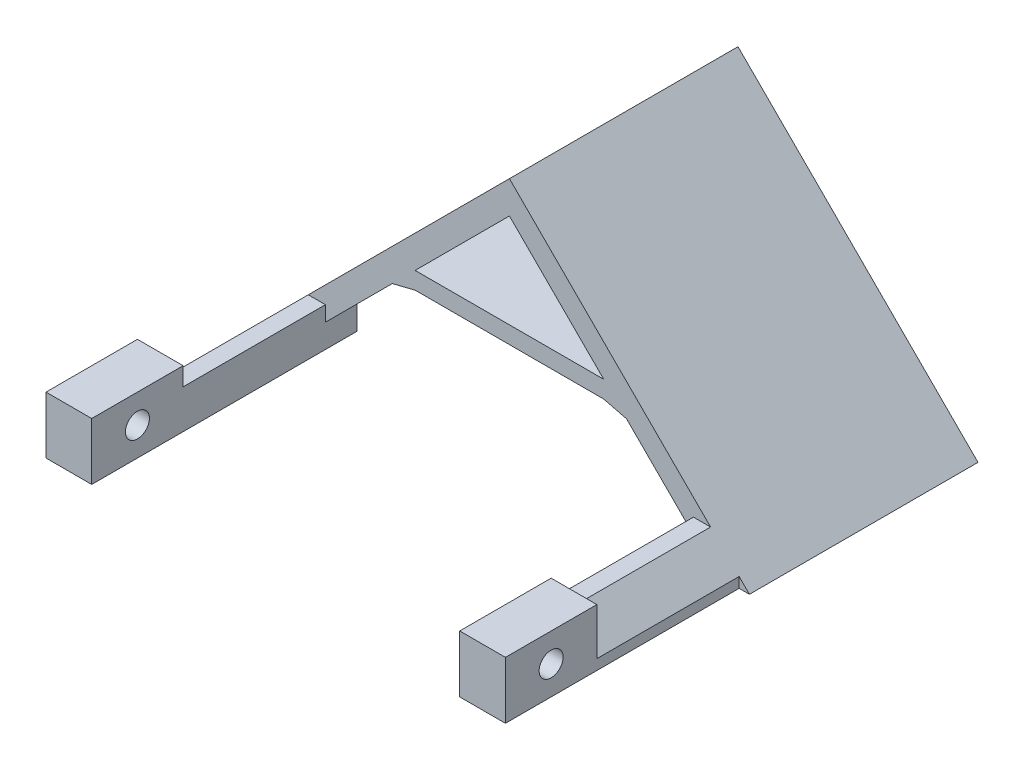
SolidWorks part; units mm, degrees
ref_plane "Front Plane" through (0, 0, 0) normal (0, 0, 1) x (1, 0, 0)
ref_plane "Top Plane" through (0, 0, 0) normal (0, 1, 0) x (1, 0, 0)
ref_plane "Right Plane" through (0, 0, 0) normal (1, 0, 0) x (0, 0, -1)
sketch "Sketch1" plane through (0, 0, 0) normal (0, 0, 1) x (1, 0, 0)
  line L1 (0, 0) -> (-42, -42)
  line L2 (0, -1000.3549) -> (0, 48999.6451) construction
  line L3 (-32.3431, -38) -> (-20.5, -26.1569)
  line L4 (32.3431, -38) -> (20.5, -26.1569)
  line L5 (0, 0) -> (42, -42)
  line L7 (-42, -42) -> (-16.5, -42) construction
  line L8 (-32.3431, -38) -> (-20.5, -38) construction
  line L9 (-34, -34) -> (34, -34) construction
  line L10 (-16.5, -42) -> (-16.5, -25.1569) construction
  line L11 (16.5, -42) -> (16.5, -25.1569) construction
  line L12 (16.5, -42) -> (42, -42) construction
  line L13 (20.5, -38) -> (32.3431, -38) construction
  line L14 (-20.5, -38) -> (-20.5, -26.1569) construction
  line L15 (20.5, -38) -> (20.5, -26.1569) construction
  line L16 (-16.5, -22.1569) -> (0, -5.6569)
  line L17 (16.5, -22.1569) -> (0, -5.6569)
  line L18 (16.5, -22.1569) -> (-16.5, -22.1569)
  line L19 (16.5, -25.1569) -> (-16.5, -25.1569)
  line L20 (-32.3431, -38) -> (-36.3431, -42)
  line L21 (-16.5, -25.1569) -> (-20.5, -26.1569)
  line L22 (16.5, -25.1569) -> (20.5, -26.1569)
  line L23 (32.3431, -38) -> (36.3431, -42)
  line L24 (-36.3431, -42) -> (-42, -42)
  line L25 (36.3431, -42) -> (42, -42)
  point P21 (0, -25.1569)
  dimension "D1" = 90
  dimension "D2" = 4
  dimension "D3" = 4
  dimension "D4" = 68
  dimension "D5" = 8
  dimension "D6" = 33
  dimension "D7" = 4
  dimension "D8" = 3
extrude "Boss-Extrude1" add sketch "Sketch1" along normal mid plane 40
sketch "Sketch5" plane through (0, 0, 20) normal (0, 0, 1) x (1, 0, 0)
  line L1 (0, 0) -> (-42, -42) construction
  line L2 (-35.2, -35.2) -> (-32.2, -35.2)
  line L3 (-32.2, -35.2) -> (-32.2, -42)
  line L5 (-32.2, -42) -> (-40.2, -42)
  line L6 (-40.2, -42) -> (-40.2, -40.2)
  line L7 (-40.2, -40.2) -> (-35.2, -35.2)
  line L8 (-40.4, 43.0678) -> (-40.4, -67) construction
  line L9 (-42, -42) -> (-36.3431, -42) construction
  dimension "D1" = 8
  dimension "D2" = 3
  dimension "D3" = 0.2
extrude "Boss-Extrude4" add sketch "Sketch5" along normal up to surface (24.9 mm away)
sketch "Sketch8" plane through (0, 0, 20) normal (0, 0, -1) x (-1, 0, 0)
  line L3 (32.2, -42) -> (36.3431, -42)
  line L4 (36.3431, -42) -> (32.2, -37.8569)
  line L5 (32.2, -37.8569) -> (32.2, -42)
  line L6 (32.2, -42) -> (36.3431, -42)
  line L7 (36.3431, -42) -> (32.2, -37.8569)
  line L8 (32.2, -37.8569) -> (32.2, -42)
  dimension "D1" = 0
extrude "Boss-Extrude6" add sketch "Sketch8" along normal blind 5.5
sketch "Sketch6" plane through (0, 0, 44.9) normal (0, 0, 1) x (1, 0, 0)
  line L0 (-40.2, -40.2) -> (-40.2, -42) construction
  line L1 (-32.2, -42) -> (-40.2, -42)
  line L2 (-32.2, -42) -> (-32.2, -32)
  line L3 (-32.2, -32) -> (-40.2, -32)
  line L4 (-40.2, -42) -> (-40.2, -32)
  line L5 (-32.2, -42) -> (-32.2, -35.2) construction
  line L6 (-40.2, -42) -> (-32.2, -42) construction
  dimension "D1" = 10
  dimension "D2" = 0
extrude "Boss-Extrude5" add sketch "Sketch6" along normal blind 16
sketch "Sketch7" plane through (-32.2, 0, 0) normal (1, 0, 0) x (0, 0, -1)
  line L0 (-60.9, -32) -> (-44.9, -32) construction
  line L1 (-60.9, -42) -> (-60.9, -32) construction
  circle A0 centre (-52.9, -37) radius 2.1
  point P5 (-52.9, -32)
  point P8 (-60.9, -37)
  dimension "D1" = 4.2
extrude "Cut-Extrude1" cut sketch "Sketch7" against normal through all
mirror "Mirror1" about plane through (0, 0, 0) normal (1, 0, 0) of "Boss-Extrude6", "Boss-Extrude4", "Boss-Extrude5", "Cut-Extrude1"
equation "\"width\"= 24"
equation "\"thk\"= 3"
equation "\"holesize\"= 4.2"
equation "\"holedistance\"= ( 20 + 12 ) / 2"
equation "\"threaded_hole\"= 3.9"
equation "\"fillet_radius\"= 2"
equation "\"ground_clearance\"= 25"
equation "\"tire_thk\"= 3"
equation "\"innerwheel_diam\" = \"wheel_diam\"-2*\"tire_thk\""
equation "\"innerwheel_thk\"= 8"
equation "\"wheel_diam\"= 2*(\"width\"/2+\"ground_clearance\")"
equation "\"coloursensor_holesize\"= 2.65"
equation "\"hole_to_edge\" = 4"
equation "\"D1@Sketch7\"=\"holesize\""
equation "\"D7@Sketch1\"=\"D2@Sketch1\""
